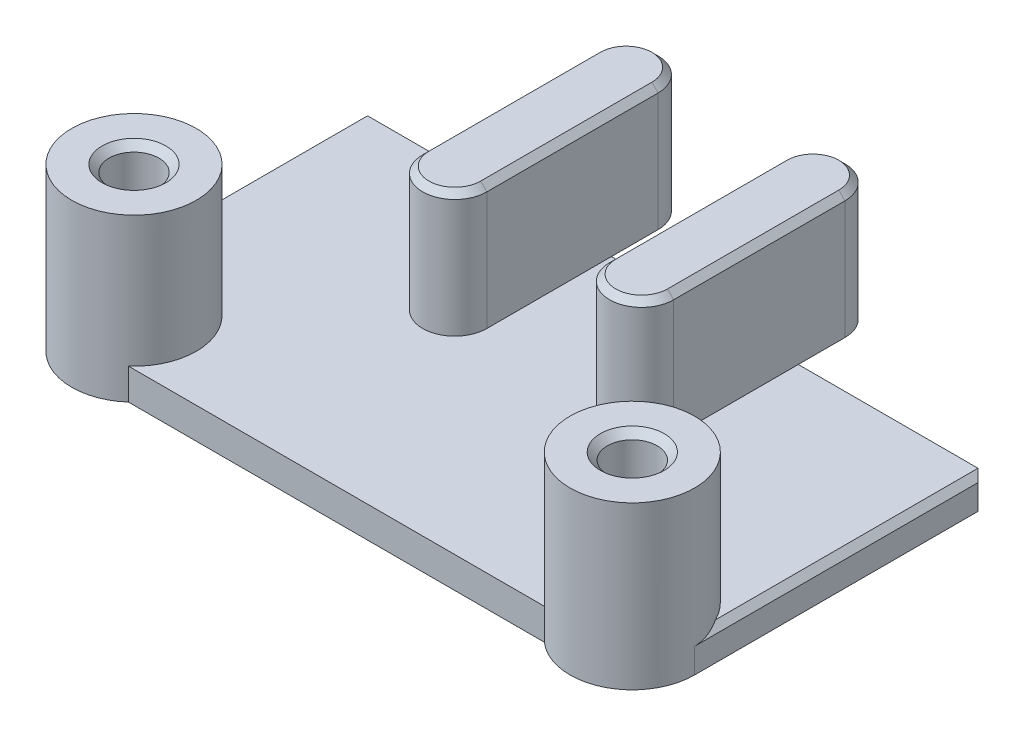
SolidWorks part; units mm, degrees
material "镁合金"
ref_plane "前视基准面" through (0, 0, 0) normal (0, 0, 1) x (1, 0, 0)
ref_plane "上视基准面" through (0, 0, 0) normal (0, 1, 0) x (1, 0, 0)
ref_plane "右视基准面" through (0, 0, 0) normal (1, 0, 0) x (0, 0, -1)
sketch "草图1" plane through (0, 0, 0) normal (0, 1, 0) x (1, 0, 0)
  line L1 (-10, 5.4) -> (10, 5.4)
  line L2 (-10, 5.4) -> (-10, -5.4)
  line L3 (-10, -5.4) -> (10, -5.4)
  line L4 (10, 5.4) -> (10, -5.4)
  line L5 (-10, 5.4) -> (10, -5.4) construction
  line L6 (-10, -5.4) -> (10, 5.4) construction
  point P0 (0, 0)
  dimension "D1" = 10.8
  dimension "D2" = 20
extrude "凸台-拉伸1" add sketch "草图1" along normal blind 1
sketch "草图5" plane through (0, 1, 0) normal (0, 1, 0) x (1, 0, 0)
  line L0 (-10, 5.4) -> (-10, -5.4) construction
  line L1 (-10, -5.4) -> (10, -5.4) construction
  circle A0 centre (-8, -3.9) radius 2
  circle A1 centre (8, -3.9) radius 2
  dimension "D1" = 4
  dimension "D2" = 4
  dimension "D3" = 16
  dimension "D4" = 1.5
extrude "凸台-拉伸3" add sketch "草图5" along normal blind 4.2 and the other way blind 1
sketch "草图6" plane through (0, 1, 0) normal (0, 1, 0) x (1, 0, 0)
  line L0 (-10, 5.4) -> (-10, -3.9) construction
  line L1 (-10, 2.4) -> (-4, 2.4)
  line L2 (-10, 2.4) -> (-10, 8.4)
  line L3 (-10, 8.4) -> (-4, 8.4)
  line L4 (-4, 2.4) -> (-4, 8.4)
  line L5 (10, 5.4) -> (-10, 5.4) construction
  line L6 (-2, 2.4) -> (2, 2.4)
  line L7 (-2, 2.4) -> (-2, 8.4)
  line L8 (-2, 8.4) -> (2, 8.4)
  line L9 (2, 2.4) -> (2, 8.4)
  line L10 (4, 2.4) -> (10, 2.4)
  line L11 (4, 2.4) -> (4, 8.4)
  line L12 (4, 8.4) -> (10, 8.4)
  line L13 (10, 2.4) -> (10, 8.4)
  dimension "D1" = 6
  dimension "D2" = 4
  dimension "D3" = 6
  dimension "D4" = 2
  dimension "D5" = 2
  dimension "D6" = 6
  dimension "D7" = 6
  dimension "D8" = 6
  dimension "D9" = 3
sketch "草图7" plane through (0, 1, 0) normal (0, 1, 0) x (1, 0, 0)
  line L0 (10, 5.4) -> (-10, 5.4) construction
  line L1 (-4.03, 9.4) -> (-1.97, 9.4)
  line L2 (-4.03, 9.4) -> (-4.03, 1.4)
  line L3 (-4.03, 1.4) -> (-1.97, 1.4)
  line L4 (-1.97, 9.4) -> (-1.97, 1.4)
  line L5 (-4.03, 9.4) -> (-1.97, 1.4) construction
  line L6 (-4.03, 1.4) -> (-1.97, 9.4) construction
  line L7 (10, 2.4) -> (10, 8.4) construction
  line L8 (1.97, 9.4) -> (4.03, 9.4)
  line L9 (1.97, 9.4) -> (1.97, 1.4)
  line L10 (1.97, 1.4) -> (4.03, 1.4)
  line L11 (4.03, 9.4) -> (4.03, 1.4)
  line L12 (1.97, 9.4) -> (4.03, 1.4) construction
  line L13 (1.97, 1.4) -> (4.03, 9.4) construction
  circle A0 centre (-3, 1.4) radius 1.03
  circle A1 centre (3, 1.4) radius 1.03
  circle A2 centre (-3, 6.9) radius 1.03
  circle A3 centre (3, 6.9) radius 1.03
  point P0 (-3, 5.4)
  point P7 (3, 5.4)
  line M8 (10, 5.4) -> (-10, 5.4)
  dimension "D7" = 1.5
  dimension "D8" = 1.5
  dimension "D9" = 2.06
  dimension "D10" = 2.06
  dimension "D1" = 7
  dimension "D2" = 2.06
  dimension "D3" = 2.06
  dimension "D4" = 7
  dimension "D5" = 8
  dimension "D6" = 8
extrude "凸台-拉伸4" add sketch "草图7" along normal blind 4 contours A0 L4 L2 M8 | L3 A0 | L3 A0 | A1 L11 L9 M8 | L10 A1 | L10 A1 | A2 L2 L4 M8 | A2 | A3 L9 L11 M8 | A3 region at (3, 1, -5.7838) region at (3, 1, -3.7962) region at (-3, 1, -5.7838) region at (-3, 1, -6.9) region at (-3, 1, -3.7962) region at (-3, 1, -1.8371) region at (-3, 1, -0.9629) region at (3, 1, -6.9) region at (3, 1, -1.8371) region at (3, 1, -0.9629)
hole_wizard "M2 螺纹孔1" positions "草图8" profile "草图9" tap size "M2" standard "GB"
sketch "草图8" plane through (0, 5.2, 0) normal (0, 1, 0) x (1, 0, 0)
  point P0 (-8, -3.9)
  point P3 (8, -3.9)
sketch "草图9" plane through (-8, 5.2, 3.9) normal (1, 0, 0) x (0, 0, 1)
  line L0 (0, 0) -> (0, 4.4807)
  line L1 (0, 4.4807) -> (0.8, 4)
  line L2 (0.8, 4) -> (0.8, 0.225)
  line L3 (0.8, 0.225) -> (1.025, 0)
  line L5 (1.025, 0) -> (0, 0)
  line L6 (-0.8, 0.225) -> (-1.025, 0) construction
  line L10 (0, 4.4807) -> (-0.8, 4) construction
  line L11 (0, -6.35) -> (0, 107.95) construction
  dimension "螺纹孔钻头直径" = 1.6
  dimension "螺纹孔钻头深度" = 4
  dimension "近端锥形沉头孔直径" = 2.05
  dimension "近端锥形沉头孔角度" = 90
  dimension "导头角度" = 118
cosmetic thread "孔螺蚊线1" parameters "D1"=3.5, "D2"=2
cosmetic thread "孔螺蚊线2" parameters "D1"=3.5, "D2"=2
sketch "草图10" plane through (0, 1, 0) normal (0, 1, 0) x (1, 0, 0)
  line L0 (-10, 2.4) -> (-10, 8.4) construction
  line L1 (10, -5.4) -> (-10, -5.4)
  line L2 (10, -5.4) -> (10, 5.4)
  line L3 (10, 5.4) -> (-10, 5.4)
  line L4 (-10, -5.4) -> (-10, 5.4)
  line L5 (10, -5.4) -> (-10, 5.4) construction
  line L6 (10, 5.4) -> (-10, -5.4) construction
  circle A0 centre (8, -3.9) radius 2 construction
  circle A1 centre (-8, -3.9) radius 2 construction
  circle A2 centre (8, -3.9) radius 2
  circle A3 centre (-8, -3.9) radius 2
  point P6 (0, 0)
extrude "切除-拉伸1" cut sketch "草图10" against normal through all contours A3 L4 L1 | A2 L1 L2 region at (9.8045, 1, 5.0389) region at (-9.8045, 1, 5.0389)
chamfer "倒角1" distance 0.2 angle 45 4 edges at (-10, 0.5, -5.4) (-10, 1, -0.75) (10, 0.5, -5.4) (10, 1, -0.75)
chamfer "倒角2" distance 0.2 angle 45 8 edges at (-3, 5, -7.93) (-1.97, 5, -4.15) (-3, 5, -0.37) (-4.03, 5, -4.15) (3, 5, -7.93) (4.03, 5, -4.15) (3, 5, -0.37) (1.97, 5, -4.15)
